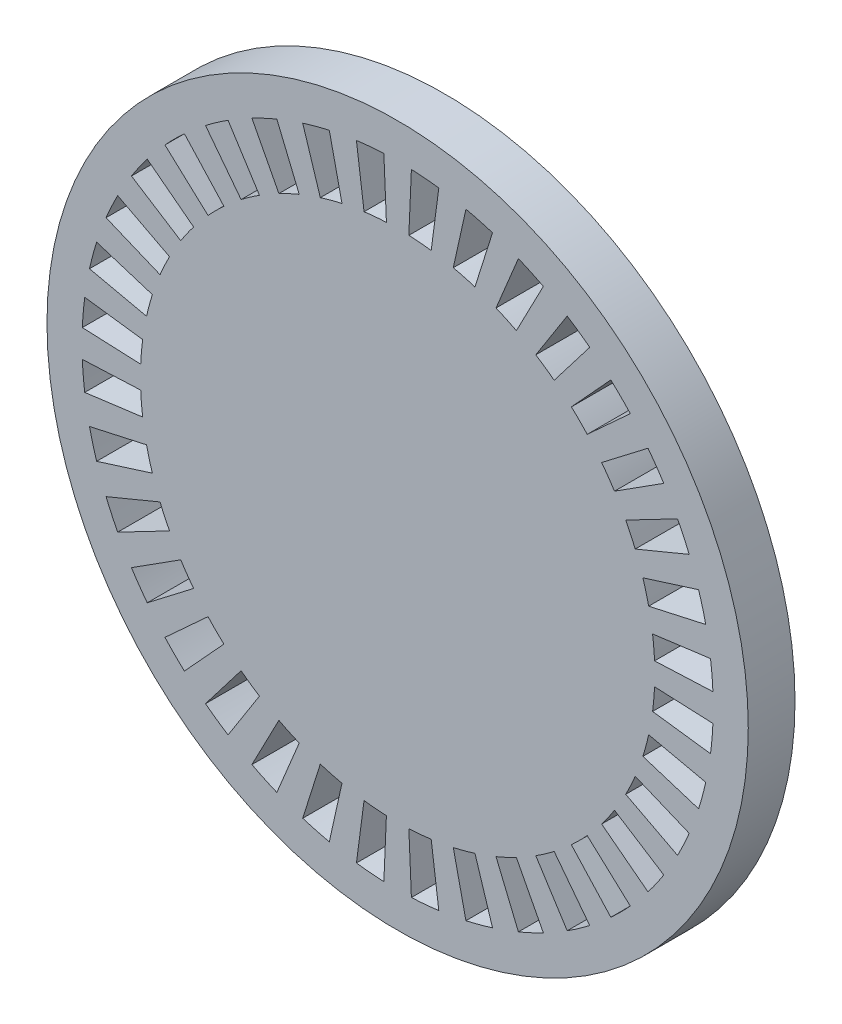
SolidWorks part; units mm, degrees
ref_plane "Plan de face" through (0, 0, 0) normal (0, 0, 1) x (1, 0, 0)
ref_plane "Plan de dessus" through (0, 0, 0) normal (0, 1, 0) x (1, 0, 0)
ref_plane "Plan de droite" through (0, 0, 0) normal (1, 0, 0) x (0, 0, -1)
sketch "Esquisse1" plane through (0, 0, 0) normal (0, 0, 1) x (1, 0, 0)
  line L0 (0, -30) -> (0, 30) construction
  line L1 (0, 0) -> (-26.9743, 1.1777) construction
  line L2 (30, 0) -> (-30, 0) construction
  line L3 (0, 0) -> (-26.9743, -1.1777) construction
  line L4 (0, 0) -> (-21.9791, 0.9596) construction
  line L5 (0, 0) -> (-21.9791, -0.9596) construction
  line L6 (-21.9791, 0.9596) -> (-26.9743, 1.1777)
  line L7 (-21.4785, 4.7617) -> (-26.36, 5.8439)
  line L8 (-21.9791, -0.9596) -> (-26.9743, -1.1777)
  line L9 (-21.8118, 2.8716) -> (-26.769, 3.5242)
  line L10 (-20.3253, 8.419) -> (-24.9447, 10.3325)
  line L11 (-20.9818, 6.6155) -> (-25.7504, 8.1191)
  line L12 (-18.5546, 11.8206) -> (-22.7716, 14.5071)
  line L13 (-19.5142, 10.1585) -> (-23.9493, 12.4672)
  line L14 (-16.2201, 14.863) -> (-19.9065, 18.2409)
  line L15 (-17.4538, 13.3928) -> (-21.4205, 16.4366)
  line L16 (-13.3928, 17.4538) -> (-16.4366, 21.4205)
  line L17 (-14.863, 16.2201) -> (-18.2409, 19.9065)
  line L18 (-10.1585, 19.5142) -> (-12.4672, 23.9493)
  line L19 (-11.8206, 18.5546) -> (-14.5071, 22.7716)
  line L20 (-6.6155, 20.9818) -> (-8.1191, 25.7504)
  line L21 (-8.419, 20.3253) -> (-10.3325, 24.9447)
  line L22 (-2.8716, 21.8118) -> (-3.5242, 26.769)
  line L23 (-4.7617, 21.4785) -> (-5.8439, 26.36)
  line L24 (0.9596, 21.9791) -> (1.1777, 26.9743)
  line L25 (-0.9596, 21.9791) -> (-1.1777, 26.9743)
  line L26 (4.7617, 21.4785) -> (5.8439, 26.36)
  line L27 (2.8716, 21.8118) -> (3.5242, 26.769)
  line L28 (8.419, 20.3253) -> (10.3325, 24.9447)
  line L29 (6.6155, 20.9818) -> (8.1191, 25.7504)
  line L30 (11.8206, 18.5546) -> (14.5071, 22.7716)
  line L31 (10.1585, 19.5142) -> (12.4672, 23.9493)
  line L32 (14.863, 16.2201) -> (18.2409, 19.9065)
  line L33 (13.3928, 17.4538) -> (16.4366, 21.4205)
  line L34 (17.4538, 13.3928) -> (21.4205, 16.4366)
  line L35 (16.2201, 14.863) -> (19.9065, 18.2409)
  line L36 (19.5142, 10.1585) -> (23.9493, 12.4672)
  line L37 (18.5546, 11.8206) -> (22.7716, 14.5071)
  line L38 (20.9818, 6.6155) -> (25.7504, 8.1191)
  line L39 (20.3253, 8.419) -> (24.9447, 10.3325)
  line L40 (21.8118, 2.8716) -> (26.769, 3.5242)
  line L41 (21.4785, 4.7617) -> (26.36, 5.8439)
  line L42 (21.9791, -0.9596) -> (26.9743, -1.1777)
  line L43 (21.9791, 0.9596) -> (26.9743, 1.1777)
  line L44 (21.4785, -4.7617) -> (26.36, -5.8439)
  line L45 (21.8118, -2.8716) -> (26.769, -3.5242)
  line L46 (20.3253, -8.419) -> (24.9447, -10.3325)
  line L47 (20.9818, -6.6155) -> (25.7504, -8.1191)
  line L48 (18.5546, -11.8206) -> (22.7716, -14.5071)
  line L49 (19.5142, -10.1585) -> (23.9493, -12.4672)
  line L50 (16.2201, -14.863) -> (19.9065, -18.2409)
  line L51 (17.4538, -13.3928) -> (21.4205, -16.4366)
  line L52 (13.3928, -17.4538) -> (16.4366, -21.4205)
  line L53 (14.863, -16.2201) -> (18.2409, -19.9065)
  line L54 (10.1585, -19.5142) -> (12.4672, -23.9493)
  line L55 (11.8206, -18.5546) -> (14.5071, -22.7716)
  line L56 (6.6155, -20.9818) -> (8.1191, -25.7504)
  line L57 (8.419, -20.3253) -> (10.3325, -24.9447)
  line L58 (2.8716, -21.8118) -> (3.5242, -26.769)
  line L59 (4.7617, -21.4785) -> (5.8439, -26.36)
  line L60 (-0.9596, -21.9791) -> (-1.1777, -26.9743)
  line L61 (0.9596, -21.9791) -> (1.1777, -26.9743)
  line L62 (-4.7617, -21.4785) -> (-5.8439, -26.36)
  line L63 (-2.8716, -21.8118) -> (-3.5242, -26.769)
  line L64 (-8.419, -20.3253) -> (-10.3325, -24.9447)
  line L65 (-6.6155, -20.9818) -> (-8.1191, -25.7504)
  line L66 (-11.8206, -18.5546) -> (-14.5071, -22.7716)
  line L67 (-10.1585, -19.5142) -> (-12.4672, -23.9493)
  line L68 (-14.863, -16.2201) -> (-18.2409, -19.9065)
  line L69 (-13.3928, -17.4538) -> (-16.4366, -21.4205)
  line L70 (-17.4538, -13.3928) -> (-21.4205, -16.4366)
  line L71 (-16.2201, -14.863) -> (-19.9065, -18.2409)
  line L72 (-19.5142, -10.1585) -> (-23.9493, -12.4672)
  line L73 (-18.5546, -11.8206) -> (-22.7716, -14.5071)
  line L74 (-20.9818, -6.6155) -> (-25.7504, -8.1191)
  line L75 (-20.3253, -8.419) -> (-24.9447, -10.3325)
  line L76 (-21.8118, -2.8716) -> (-26.769, -3.5242)
  line L77 (-21.4785, -4.7617) -> (-26.36, -5.8439)
  circle A0 centre (0, 0) radius 30
  circle A1 centre (0, 0) radius 27
  circle A2 centre (0, 0) radius 22
  dimension "D1" = 60
  dimension "D2" = 3
  dimension "D3" = 5
  dimension "D4" = 2.5
  dimension "D5" = 36
extrude "Boss.-Extru.1" add sketch "Esquisse1" along normal blind 4 contours A2 | A0 A1 | A2 L6 A1 L8 | A2 L7 A1 L9 | A2 L10 A1 L11 | A2 L12 A1 L13 | A2 L14 A1 L15 | A2 L16 A1 L17 | A2 L18 A1 L19 | A2 L20 A1 L21 | A2 L22 A1 L23 | A2 L24 A1 L25 | A2 L26 A1 L27 | A2 L28 A1 L29 | A2 L30 A1 L31 | A2 L32 A1 L33 | A2 L34 A1 L35 | A2 L36 A1 L37 | A2 L38 A1 L39 | A2 L40 A1 L41 | A2 L42 A1 L43 | A2 L44 A1 L45 | A2 L46 A1 L47 | A2 L48 A1 L49 | A2 L50 A1 L51 | A2 L52 A1 L53 | A2 L54 A1 L55 | A2 L56 A1 L57 | A2 L58 A1 L59 | A2 L60 A1 L61 | A2 L62 A1 L63 | A2 L64 A1 L65 | A2 L66 A1 L67 | A2 L68 A1 L69 | A2 L70 A1 L71 | A2 L72 A1 L73 | A2 L74 A1 L75 | A2 L76 A1 L77 region at (-24.5772, 0, 0) region at (0, 0, 0) region at (-24.2039, 4.2678, 0) region at (-24.2039, -4.2678, 0) region at (-23.095, 8.4059, 0) region at (-23.095, -8.4059, 0) region at (-21.2845, 12.2886, 0) region at (-21.2845, -12.2886, 0) region at (-18.8273, 15.7979, 0) region at (-18.8273, -15.7979, 0) region at (-15.7979, 18.8273, 0) region at (-15.7979, -18.8273, 0) region at (-12.2886, 21.2845, 0) region at (-12.2886, -21.2845, 0) region at (-8.4059, 23.095, 0) region at (-8.4059, -23.095, 0) region at (-4.2678, 24.2039, 0) region at (-4.2678, -24.2039, 0) region at (0, 24.5772, 0) region at (0, -24.5772, 0) region at (4.2678, 24.2039, 0) region at (4.2678, -24.2039, 0) region at (8.4059, 23.095, 0) region at (8.4059, -23.095, 0) region at (12.2886, 21.2845, 0) region at (12.2886, -21.2845, 0) region at (15.7979, 18.8273, 0) region at (15.7979, -18.8273, 0) region at (18.8273, 15.7979, 0) region at (18.8273, -15.7979, 0) region at (21.2845, 12.2886, 0) region at (21.2845, -12.2886, 0) region at (23.095, 8.4059, 0) region at (23.095, -8.4059, 0) region at (24.2039, 4.2678, 0) region at (24.2039, -4.2678, 0) region at (24.5772, 0, 0) region at (-29.1515, 0, 0)
